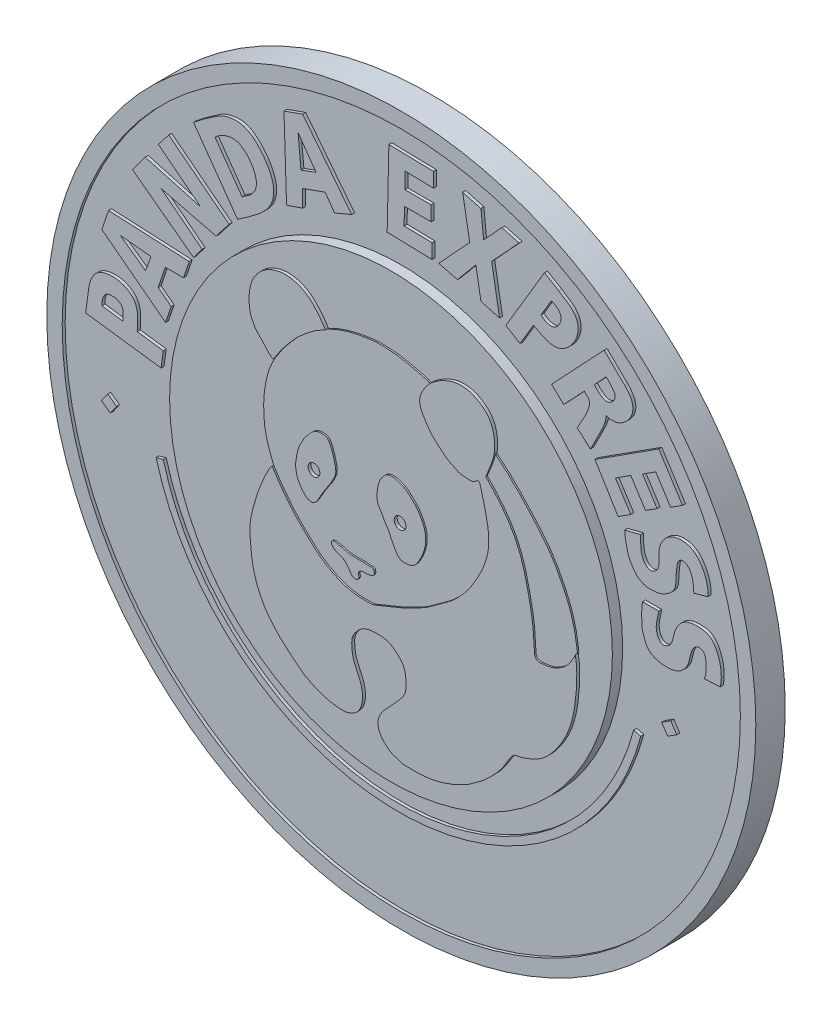
SolidWorks part; units mm, degrees
ref_plane "Front Plane" through (0, 0, 0) normal (0, 0, 1) x (1, 0, 0)
ref_plane "Top Plane" through (0, 0, 0) normal (0, 1, 0) x (1, 0, 0)
ref_plane "Right Plane" through (0, 0, 0) normal (1, 0, 0) x (0, 0, -1)
sketch "Sketch1" plane through (0, 0, 0) normal (0, 0, 1) x (1, 0, 0)
  line L0 (339.332, 1068.0205) -> (1796.7089, 1068.0205) construction
  line L1 (-19.4812, -2.2291) -> (-19.0488, -1.6286)
  line L2 (-19.4812, -2.2291) -> (-18.8807, -2.6615)
  line L3 (-19.0488, -1.6286) -> (-18.4483, -2.061)
  line L4 (-18.8807, -2.6615) -> (-18.4483, -2.061)
  line L5 (-19.265, -1.9289) -> (-18.6645, -2.3612) construction
  line L6 (-19.1809, -2.4453) -> (-18.7486, -1.8448) construction
  line L7 (-16.328, 0.8095) -> (-21.4546, 1.493)
  line L8 (18.5982, -2.1307) -> (19.2216, -1.7319)
  line L9 (18.5982, -2.1307) -> (19.007, -2.7476)
  line L10 (19.2216, -1.7319) -> (19.6303, -2.3488)
  line L11 (19.007, -2.7476) -> (19.6303, -2.3488)
  line L12 (-16.328, 0.8095) -> (-16.1813, 1.9098)
  line L13 (-21.4546, 1.493) -> (-21.3079, 2.5933)
  line L14 (-16.1813, 1.9098) -> (-17.9511, 2.1457)
  line L15 (-20.356, 2.4664) -> (-18.9346, 2.2769) construction
  line L16 (-18.9346, 2.2769) -> (-20.356, 2.4664)
  line L17 (-16.0257, 3.645) -> (-20.356, 6.9532)
  line L18 (-20.356, 6.9532) -> (-19.8974, 8.3016)
  line L19 (-19.8974, 8.3016) -> (-14.4158, 8.0372)
  line L20 (-14.4158, 8.0372) -> (-14.8071, 6.8869)
  line L21 (-14.8071, 6.8869) -> (-16.0419, 6.8869)
  line L22 (-16.0419, 6.8869) -> (-16.5291, 5.4546)
  line L23 (-16.5291, 5.4546) -> (-15.641, 4.7761)
  line L24 (-15.641, 4.7761) -> (-16.0257, 3.645)
  line L25 (-17.3832, 6.0121) -> (-19.0928, 7.2323)
  line L26 (-19.0928, 7.2323) -> (-17.016, 7.029)
  line L27 (-17.016, 7.029) -> (-17.3832, 6.0121)
  line L28 (-14.1219, 8.4186) -> (-18.2734, 11.5238)
  line L29 (-18.2734, 11.5238) -> (-17.4049, 12.685)
  line L30 (-17.4049, 12.685) -> (-13.6436, 11.6434)
  line L31 (-13.6436, 11.6434) -> (-16.5148, 13.8822)
  line L32 (-16.5148, 13.8822) -> (-15.8076, 14.7891)
  line L33 (-15.8076, 14.7891) -> (-11.7035, 11.5889)
  line L34 (-11.7035, 11.5889) -> (-12.5951, 10.4454)
  line L35 (-12.5951, 10.4454) -> (-16.3291, 11.3794)
  line L36 (-16.3291, 11.3794) -> (-13.5362, 9.2016)
  line L37 (-13.5362, 9.2016) -> (-14.1219, 8.4186)
  line L38 (-14.1219, 16.3735) -> (-11.1297, 12.1624)
  line L39 (-12.6612, 16.238) -> (-10.818, 13.644)
  line L40 (-7.7996, 14.6612) -> (-7.9742, 20.1206)
  line L41 (-7.9742, 20.1206) -> (-6.7044, 20.5722)
  line L42 (-6.7044, 20.5722) -> (-3.3753, 16.3234)
  line L43 (-4.5395, 15.8336) -> (-3.3753, 16.3234)
  line L44 (-4.5395, 15.8336) -> (-5.172, 16.7407)
  line L45 (-5.172, 16.7407) -> (-6.7044, 16.1956)
  line L46 (-6.7044, 16.1956) -> (-6.7044, 15.0331)
  line L47 (-6.7044, 15.0331) -> (-7.7996, 14.6612)
  line L48 (-6.8197, 17.2168) -> (-7.0148, 19.3221)
  line L49 (-7.0148, 19.3221) -> (-5.7899, 17.5994)
  line L50 (-5.7899, 17.5994) -> (-6.8197, 17.2168)
  line L51 (-0.8441, 21.7149) -> (-0.9604, 16.4903)
  line L52 (-0.8441, 21.7149) -> (0.2954, 21.6896)
  line L53 (-0.9604, 16.4903) -> (0.1792, 16.4649)
  line L54 (0.2635, 20.7001) -> (0.2389, 19.599)
  line L55 (0.2954, 21.6896) -> (2.1953, 21.6473)
  line L56 (2.1953, 21.6473) -> (2.1953, 20.6571)
  line L57 (2.1953, 20.6571) -> (0.2635, 20.7001)
  line L58 (0.2389, 19.599) -> (2.0359, 19.599)
  line L59 (2.0359, 19.599) -> (2.0359, 18.6011)
  line L60 (2.0359, 18.6011) -> (0.2167, 18.6011)
  line L61 (0.1909, 17.4402) -> (2.0962, 17.3978)
  line L62 (2.0962, 17.3978) -> (2.0962, 16.4105)
  line L63 (2.0962, 16.4105) -> (0.1792, 16.4649)
  line L64 (0.2167, 18.6011) -> (0.1909, 17.4402)
  line L65 (2.5434, 16.4105) -> (4.6494, 18.6907)
  line L66 (4.6494, 18.6907) -> (4.1742, 21.4149)
  line L67 (4.1742, 21.4149) -> (5.415, 21.0757)
  line L68 (5.415, 21.0757) -> (5.5944, 19.3138)
  line L69 (5.5944, 19.3138) -> (6.838, 20.6601)
  line L70 (6.838, 20.6601) -> (8.007, 20.3405)
  line L71 (8.007, 20.3405) -> (6.1448, 18.3245)
  line L72 (6.1448, 18.3245) -> (6.6794, 15.2603)
  line L73 (6.6794, 15.2603) -> (5.415, 15.6059)
  line L74 (5.415, 15.6059) -> (5.0699, 17.5842)
  line L75 (5.0699, 17.5842) -> (3.8207, 16.0897)
  line L76 (3.8207, 16.0897) -> (2.5434, 16.4105)
  line L77 (7.1051, 15.0331) -> (9.7332, 19.4533)
  line L78 (7.1051, 15.0331) -> (8.0751, 14.4563)
  line L79 (9.7332, 19.4533) -> (10.7033, 18.8765)
  line L80 (8.0751, 14.4563) -> (8.9844, 15.9855)
  line L81 (9.4951, 16.8446) -> (10.2149, 18.0551)
  line L82 (10.2149, 13.128) -> (13.7859, 16.9193)
  line L83 (13.7859, 16.9193) -> (15.1877, 15.5557)
  line L84 (12.8569, 10.6327) -> (11.9562, 11.4358)
  line L85 (10.2149, 13.128) -> (11.0408, 12.3501)
  line L86 (11.0408, 12.3501) -> (12.4388, 13.8344)
  line L87 (13.1299, 14.5705) -> (13.9228, 15.421)
  line L88 (13.163, 10.177) -> (17.5041, 12.9619)
  line L89 (17.5041, 12.9619) -> (19.1158, 10.4495)
  line L90 (19.1158, 10.4495) -> (18.31, 9.9325)
  line L91 (18.31, 9.9325) -> (17.2969, 11.5117)
  line L92 (17.2969, 11.5117) -> (16.4026, 10.938)
  line L93 (16.4026, 10.938) -> (17.3902, 9.3984)
  line L94 (17.3902, 9.3984) -> (16.6002, 8.8916)
  line L95 (16.6002, 8.8916) -> (15.6008, 10.4495)
  line L96 (15.6008, 10.4495) -> (14.5586, 9.7809)
  line L97 (14.5586, 9.7809) -> (15.6008, 8.1562)
  line L98 (15.6008, 8.1562) -> (14.7409, 7.6046)
  line L99 (14.7409, 7.6046) -> (13.163, 10.177)
  line L100 (19.8907, 5.6627) -> (20.842, 5.9313)
  line L101 (15.1877, 7.029) -> (16.2747, 7.3088)
  line L102 (21.6804, 1.0421) -> (20.6063, 0.9853)
  line L103 (16.4026, 3.4174) -> (17.5041, 3.4174)
  line L104 (-16.4657, -4.4254) -> (-15.9828, -4.2956)
  line L105 (15.9993, -4.2338) -> (16.4827, -4.3617)
  line L106 (-19.7778, -8.1941) -> (-18.3448, -7.6877)
  line L107 (-18.3448, -7.6877) -> (-18.7074, -6.6618)
  line L108 (-18.7074, -6.6618) -> (-19.1206, -6.8078)
  line L109 (-19.1206, -6.8078) -> (-18.9255, -7.36)
  line L110 (-18.9255, -7.36) -> (-19.3406, -7.5067)
  line L111 (-17.2786, -7.2591) -> (-17.7047, -7.4011)
  circle A0 centre (0, 0) radius 24.1
  circle A2 centre (0.8192, 0.7097) radius 0.4
  circle A3 centre (-5.0357, 0.9092) radius 0.4
  circle A4 centre (0, 0) radius 23.05
  arc A8 (-16.4657, -4.4254) -> (16.4827, -4.3617) centre (0, 0) ccw
  arc A9 (12.0045, 11.3927) -> (11.9591, 11.4404) centre (0, 0) ccw
  arc A10 (-15.9828, -4.2956) -> (15.9993, -4.2338) centre (0, 0) ccw
  circle A11 centre (0, 0) radius 15.05
  spline S0 degree 3 poles (-21.3079, 2.5933) (-21.2691, 3.0317) (-21.1768, 3.6983) (-20.5495, 4.4203) (-19.7315, 4.6028) (-18.8263, 4.4892) (-17.7876, 3.7164) (-17.9169, 2.6645) (-17.9511, 2.1457) knots 0 0 0 0 0.212608 0.302228 0.435295 0.58816 0.72772 1 1 1 1
  spline S1 degree 3 poles (-20.356, 2.4664) (-20.3596, 2.708) (-20.3083, 3.0361) (-20.0437, 3.3225) (-19.8441, 3.3874) (-19.6429, 3.3957) (-19.4314, 3.3931) (-19.2421, 3.3315) (-19.0854, 3.2283) (-18.9615, 3.0995) (-18.903, 2.9079) (-18.9209, 2.6293) (-18.9309, 2.419) (-18.9346, 2.2769) knots 0 0 0 0 0.24967 0.31684 0.388224 0.45752 0.523447 0.60401 0.657003 0.715094 0.783365 0.85461 1 1 1 1
  spline S2 degree 3 poles (-14.1219, 16.3735) (-13.7209, 16.7208) (-13.0883, 17.1571) (-12.271, 17.7302) (-11.5963, 17.9267) (-10.9205, 17.9501) (-10.2597, 17.6972) (-9.7098, 17.2041) (-9.2288, 16.6239) (-8.862, 15.963) (-8.6469, 15.3064) (-8.6778, 14.6592) (-8.8637, 14.1319) (-9.1362, 13.7413) (-9.417, 13.4477) (-9.7019, 13.1931) (-10.037, 12.9534) (-10.3472, 12.697) (-10.7324, 12.4509) (-10.9743, 12.2645) (-11.1297, 12.1624) knots 0 0 0 0 0.137806 0.202861 0.258965 0.319388 0.376747 0.439138 0.510699 0.573298 0.636319 0.688639 0.739908 0.780606 0.812336 0.846158 0.880461 0.92011 0.951368 1 1 1 1
  spline S3 degree 3 poles (-12.6612, 16.238) (-12.4563, 16.4417) (-12.1084, 16.6477) (-11.5932, 16.7783) (-11.2363, 16.7638) (-10.8923, 16.6366) (-10.6281, 16.4146) (-10.3806, 16.2025) (-10.2419, 15.9574) (-10.08, 15.7506) (-9.9673, 15.4995) (-9.8712, 15.2122) (-9.8326, 14.8948) (-9.8834, 14.5632) (-10.0424, 14.2696) (-10.3388, 13.9337) (-10.6484, 13.7894) (-10.818, 13.644) knots 0 0 0 0 0.150292 0.209994 0.278717 0.335693 0.400225 0.460062 0.506204 0.547788 0.598508 0.650561 0.70761 0.76587 0.824644 0.881692 1 1 1 1
  spline S4 degree 3 poles (-7.8698, -0.2966) (-8.0954, 0.2301) (-8.4492, 1.1743) (-8.5703, 2.5467) (-8.5515, 3.6093) (-8.3835, 4.488) (-8.1929, 5.2865) (-7.9297, 5.779) (-7.7996, 6.0464) knots 0 0 0 0 0.262924 0.455258 0.626555 0.746828 0.863807 1 1 1 1
  spline S5 degree 3 poles (-7.7996, 6.0464) (-7.6451, 6.2665) (-7.4204, 6.6545) (-7.0465, 7.1537) (-6.6804, 7.5866) (-6.3099, 8.0223) (-5.8659, 8.4497) (-5.3867, 8.825) (-4.8971, 9.2131) (-4.387, 9.4734) (-3.8724, 9.7419) (-3.2734, 9.9751) (-2.5437, 10.1984) (-1.7558, 10.3499) (-0.7272, 10.5033) (0.028, 10.4188) (0.517, 10.391) knots 0 0 0 0 0.080975 0.134778 0.187605 0.25173 0.306954 0.372796 0.435137 0.494459 0.544747 0.60996 0.687673 0.774238 0.851502 1 1 1 1
  spline S6 degree 3 poles (0.517, 10.391) (0.7571, 10.363) (1.1301, 10.2878) (1.6851, 10.1723) (2.1805, 10.0244) (2.5544, 9.9487) (2.7165, 9.8349) knots 0 0 0 0 0.318288 0.501169 0.746278 1 1 1 1
  spline S7 degree 3 poles (2.7165, 9.8349) (2.7585, 9.8259) (2.7327, 9.8017) (2.6898, 9.7669) (2.6476, 9.7124) (2.603, 9.6398) (2.5377, 9.5744) (2.4953, 9.4826) (2.4254, 9.3973) (2.3776, 9.2895) (2.3059, 9.1789) (2.2534, 9.0434) (2.1887, 8.8944) (2.1538, 8.732) (2.1435, 8.5478) (2.1783, 8.3137) (2.2639, 8.0294) (2.4362, 7.7403) (2.6287, 7.4486) (2.8286, 7.1514) (3.0779, 6.8852) (3.3548, 6.607) (3.69, 6.3213) (4.0714, 6.0472) (4.481, 5.8298) (4.913, 5.6227) (5.3993, 5.6193) (5.838, 5.5698) (6.0966, 5.905) (6.2435, 5.7688) (6.27, 5.658) (6.3218, 5.5071) (6.3605, 5.3336) (6.4745, 4.9931) (6.5291, 4.6383) (6.6488, 4.174) (6.8141, 3.4444) (6.8792, 2.7588) (6.819, 2.2769) knots 0 0 0 0 0.004783 0.008508 0.016209 0.023904 0.032742 0.042051 0.052291 0.063813 0.075279 0.089559 0.104863 0.1213 0.136341 0.156965 0.188092 0.219871 0.251904 0.287379 0.321184 0.355103 0.398707 0.445985 0.487792 0.530607 0.579554 0.623786 0.654803 0.659487 0.677019 0.686171 0.704891 0.727287 0.787897 0.806239 0.863282 1 1 1 1
  spline S8 degree 3 poles (6.819, 2.2769) (6.819, 2.0161) (6.7092, 1.6228) (6.5071, 0.999) (6.2546, 0.4026) (5.9145, -0.1762) (5.4655, -0.9295) (4.8863, -1.5979) (4.1145, -2.3101) (3.3615, -2.7838) (2.6307, -3.396) (1.8173, -3.786) (1.0012, -4.215) (0.2125, -4.521) (-0.4801, -4.7998) (-0.967, -5.0314) (-1.4954, -5.0428) (-2.1511, -5.0376) (-2.9852, -4.8681) (-3.7859, -4.5156) (-4.6591, -3.9915) (-5.5404, -3.1815) (-6.7534, -1.9752) (-7.4558, -0.951) (-7.8698, -0.2966) knots 0 0 0 0 0.038566 0.060844 0.098257 0.135206 0.161303 0.229508 0.266609 0.318218 0.362343 0.408696 0.452572 0.500532 0.534926 0.565086 0.579479 0.613416 0.663457 0.705415 0.743958 0.815443 0.883791 1 1 1 1
  spline S9 degree 3 poles (-7.7996, 6.0464) (-8.1142, 6.1934) (-8.4061, 6.6917) (-8.9684, 7.1134) (-9.1868, 7.5516) (-9.3506, 7.8873) (-9.4347, 8.3363) (-9.4676, 8.9461) (-9.3813, 9.6739) (-9.0254, 10.4197) (-8.4574, 11.0181) (-7.6635, 11.3928) (-6.6098, 11.5101) (-5.4899, 11.0879) (-4.7556, 10.2648) (-4.3819, 9.7678) (-4.2674, 9.5361) knots 0 0 0 0 0.091045 0.156662 0.189319 0.225208 0.259759 0.314673 0.394281 0.459416 0.540292 0.617479 0.697593 0.828696 0.928545 1 1 1 1
  spline S10 degree 3 poles (2.742, 9.8124) (2.8815, 9.9916) (3.2342, 10.2729) (3.8223, 10.6189) (4.495, 10.8717) (5.3292, 10.9228) (6.1699, 10.5971) (6.965, 9.9438) (7.2573, 8.9642) (7.269, 7.9936) (6.9947, 7.1881) (6.785, 6.6958) (6.6353, 6.3436) (6.7624, 6.2308) (6.895, 6.0725) (7.017, 5.9709) (7.1051, 5.8757) knots 0 0 0 0 0.074542 0.147752 0.224877 0.309979 0.41722 0.515404 0.639072 0.738685 0.83491 0.910197 0.931048 0.943333 0.961579 1 1 1 1
  spline S11 degree 3 poles (-7.8698, -0.2966) (-7.9669, -0.372) (-8.1093, -0.5873) (-8.3686, -1.1056) (-8.609, -1.6814) (-8.8668, -2.3248) (-9.0417, -2.9481) (-9.264, -3.6956) (-9.4298, -4.5934) (-9.3613, -5.4091) (-9.3053, -6.1456) (-9.1931, -6.8564) (-8.9337, -7.8216) (-8.3664, -8.9775) (-7.4864, -10.0166) (-6.5688, -10.7863) (-5.8603, -11.3886) (-5.1793, -11.7627) (-4.367, -12.1085) (-3.5858, -12.2564) (-2.8615, -12.2789) (-2.4465, -12.1255) (-1.8999, -11.7656) (-1.687, -10.9971) (-1.7828, -10.2013) (-2.0566, -9.5521) (-2.3907, -8.9202) (-2.4659, -8.2782) (-2.4794, -7.7623) (-2.3011, -7.3166) (-2.039, -7.0486) (-1.7478, -6.7699) (-1.495, -6.6845) (-1.1715, -6.5969) (-0.8714, -6.5881) (-0.5143, -6.5754) (-0.1409, -6.6304) (0.2891, -6.7936) (0.7059, -7.1433) (1.131, -7.6086) (1.225, -8.2488) (1.2466, -8.8123) (1.1152, -9.3303) (0.8325, -9.6422) (0.441, -10.1058) (-0.006, -10.5386) (-0.4673, -11.0901) (-0.7105, -11.5884) (-0.6845, -12.0178) (-0.5581, -12.3443) (-0.4095, -12.6017) (-0.1202, -12.8828) (0.2279, -13.1621) (0.6218, -13.2389) (0.9291, -13.3723) (1.2092, -13.4066) (1.5533, -13.3952) (1.9399, -13.403) (2.3733, -13.3907) (2.8331, -13.3379) (3.2975, -13.246) (3.7367, -13.1264) (4.1564, -12.9826) (4.542, -12.8403) (4.9967, -12.5882) (5.4073, -12.4174) (5.6956, -12.1817) (5.9279, -12.0253) (6.3206, -11.7521) (7.048, -11.0999) (7.8304, -10.2552) (8.2495, -9.4122) (8.5575, -9.0662) (8.7914, -9.0098) (9.1141, -8.9679) (9.478, -8.8285) (9.9237, -8.6465) (10.352, -8.4183) (10.894, -7.9721) (11.468, -7.2875) (11.9927, -6.4407) (12.5497, -5.1606) (12.8285, -3.3719) (12.8686, -1.8572) (12.7298, -1.0883) knots 0 0 0 0 0.007011 0.014783 0.033549 0.043071 0.054853 0.070952 0.088248 0.107232 0.118017 0.131016 0.148787 0.175674 0.20476 0.226792 0.244992 0.258357 0.271565 0.29594 0.303926 0.313058 0.321071 0.341004 0.354332 0.367388 0.381474 0.395309 0.404361 0.410961 0.422437 0.425735 0.43417 0.437336 0.44516 0.45138 0.458007 0.466877 0.477543 0.48934 0.502235 0.513644 0.522123 0.532268 0.537492 0.557326 0.568112 0.579108 0.58845 0.591926 0.59936 0.605375 0.61525 0.624546 0.628148 0.63458 0.64061 0.648096 0.656937 0.665671 0.674836 0.684305 0.691972 0.700514 0.708012 0.722054 0.725913 0.729489 0.738257 0.753548 0.786033 0.803683 0.808277 0.811877 0.817215 0.827205 0.834171 0.845129 0.855095 0.874603 0.896509 0.912539 0.955058 1 1 1 1
  spline S12 degree 3 poles (12.7298, -1.0883) (12.6797, -1.2231) (12.56, -1.4426) (12.2508, -1.9657) (11.7266, -2.393) (11.0363, -2.6958) (10.5826, -2.7318) (10.2423, -2.7706) (10.0738, -2.6715) (9.9407, -2.5319) (9.966, -2.3796) (9.9456, -2.2453) (9.9426, -2.0798) (9.9261, -1.8665) (9.8968, -1.4785) (9.8741, -1.0693) (9.7722, -0.1933) (9.5358, 0.9691) (9.1873, 2.4844) (8.6476, 3.8078) (7.9718, 4.8579) (7.4802, 5.4523) (7.2443, 5.7152) knots 0 0 0 0 0.034675 0.060301 0.146525 0.192052 0.240064 0.257138 0.271971 0.286029 0.300164 0.306563 0.318999 0.339993 0.358311 0.413001 0.438973 0.571315 0.699318 0.81421 0.914445 1 1 1 1
  spline S13 degree 3 poles (7.1051, 5.8757) (7.1279, 5.8511) (7.1758, 5.7989) (7.2194, 5.743) (7.2443, 5.7152) knots 0 0 0 0 0.474339 1 1 1 1
  spline S14 degree 3 poles (7.2065, 7.9328) (7.2419, 7.8726) (7.3373, 7.765) (7.537, 7.6278) (7.7636, 7.3937) (8.0698, 7.1947) (8.28, 6.9221) (8.4856, 6.7412) (8.69, 6.5563) (8.8995, 6.3265) (9.1296, 6.0794) (9.4861, 5.7124) (9.8089, 5.3025) (10.1801, 4.9279) (10.4244, 4.6174) (10.7123, 4.2695) (10.9886, 3.8516) (11.2824, 3.4158) (11.5191, 2.9264) (11.801, 2.4395) (12.0053, 1.9288) (12.222, 1.4589) (12.3778, 0.9725) (12.5313, 0.4458) (12.651, -0.1163) (12.7048, -0.6277) (12.7981, -0.9652) (12.7298, -1.0883) knots 0 0 0 0 0.019122 0.039215 0.066393 0.108561 0.138517 0.160369 0.183882 0.214401 0.245895 0.276915 0.355239 0.389296 0.421963 0.463986 0.513572 0.559828 0.608533 0.663052 0.71455 0.759793 0.805469 0.854908 0.911185 0.962305 1 1 1 1
  spline S15 degree 3 poles (-5.8531, 2.1457) (-5.8137, 2.1982) (-5.7778, 2.3755) (-5.5778, 2.5904) (-5.3744, 2.8763) (-5.0924, 3.1386) (-4.748, 3.3433) (-4.4246, 3.3105) (-4.1622, 3.3021) (-4.0161, 3.1106) (-3.8488, 2.7995) (-3.7001, 2.3487) (-3.5662, 1.8312) (-3.5309, 1.4066) (-3.7025, 1.0683) (-3.8202, 0.7985) (-4.0638, 0.4685) (-4.3018, 0.0853) (-4.6463, -0.4561) (-4.8253, -0.8829) (-5.0593, -1.0351) knots 0 0 0 0 0.027214 0.073863 0.120798 0.175728 0.237147 0.280267 0.312444 0.341416 0.37515 0.464016 0.53885 0.60401 0.635554 0.697289 0.728278 0.808417 0.88794 1 1 1 1
  spline S16 degree 3 poles (-5.0593, -1.0351) (-5.1488, -1.084) (-5.296, -1.0515) (-5.4843, -1.0019) (-5.6583, -0.868) (-5.837, -0.669) (-6.0659, -0.3455) (-6.221, 0.0555) (-6.3054, 0.5295) (-6.244, 1.0146) (-6.1494, 1.4999) (-6.0165, 1.8943) (-5.8955, 2.0894) (-5.8531, 2.1457) knots 0 0 0 0 0.072528 0.112402 0.148382 0.238596 0.317746 0.451456 0.565272 0.683898 0.823832 0.946187 1 1 1 1
  spline S17 degree 3 poles (-3.8049, -2.9373) (-3.856, -2.8116) (-3.8647, -2.6966) (-3.755, -2.6053) (-3.5802, -2.5829) (-3.3791, -2.6817) (-3.1383, -2.6805) (-2.8611, -2.7796) (-2.5219, -2.8411) (-2.0754, -2.8499) (-1.5965, -2.8326) (-1.2558, -2.8728) (-0.9613, -2.8792) (-0.9425, -2.9959) (-0.9276, -3.1123) (-0.9574, -3.2911) (-1.1954, -3.37) (-1.442, -3.4336) (-1.7167, -3.3825) (-1.9185, -3.4731) (-2.0427, -3.6436) (-1.9591, -3.8304) (-2.0161, -4.0345) (-2.1944, -4.1119) (-2.4309, -4.0847) (-2.5621, -3.8441) (-2.7332, -3.6292) (-2.9128, -3.411) (-3.1621, -3.2276) (-3.4418, -3.1858) (-3.6759, -3.0608) (-3.8049, -2.9373) (-3.856, -2.8116) (-3.8647, -2.6966) knots -0.069641 -0.0386 -0.005489 0 0.017312 0.037391 0.051206 0.088306 0.125243 0.148544 0.208577 0.265756 0.332972 0.400272 0.42114 0.43379 0.44282 0.471286 0.497085 0.537674 0.577476 0.607463 0.623843 0.658289 0.682487 0.701901 0.73331 0.770198 0.806365 0.848099 0.885786 0.930359 0.9614 0.994511 1 1.017312 1.037391 1.051206 only from (-3.8442, -2.8376) to (-3.8442, -2.8376)
  spline S18 degree 3 poles (-0.7138, 1.0524) (-0.7458, 1.3812) (-0.7605, 1.6915) (-0.7005, 2.0488) (-0.6214, 2.448) (-0.3838, 2.8453) (-0.0835, 3.147) (0.3836, 3.2107) (0.8128, 3.0761) (1.2487, 2.8736) (1.5796, 2.5436) (1.9609, 2.1911) (2.2655, 1.702) (2.5565, 1.0762) (2.5938, 0.3573) (2.3868, -0.3333) (2.1319, -0.856) (1.8112, -1.3429) (1.32, -1.5002) (0.7796, -1.4799) (0.4925, -1.0312) (0.2404, -0.6025) (0.0577, -0.1057) (-0.2756, 0.3043) (-0.438, 0.7306) (-0.7138, 1.0524) (-0.7458, 1.3812) (-0.7605, 1.6915) knots -0.10057 -0.055269 -0.031008 0 0.021936 0.04495 0.087916 0.119709 0.157131 0.186449 0.229202 0.26531 0.302252 0.341943 0.391484 0.441273 0.508862 0.560753 0.615141 0.651568 0.697769 0.734975 0.772439 0.817527 0.85896 0.89943 0.944731 0.968992 1 1.021936 1.04495 1.087916 only from (-0.7455, 1.4167) to (-0.7455, 1.4167)
  spline S19 degree 3 poles (10.7033, 18.8765) (10.9761, 18.6947) (11.4462, 18.4434) (11.959, 17.8662) (12.0828, 17.1068) (11.7876, 16.3466) (11.2829, 15.7715) (10.6982, 15.4417) (10.1171, 15.4592) (9.5478, 15.6787) (9.2006, 15.8769) (8.9844, 15.9855) knots 0 0 0 0 0.155202 0.252119 0.353417 0.502545 0.622306 0.711778 0.810984 0.885243 1 1 1 1
  spline S20 degree 3 poles (10.2149, 18.0551) (10.3341, 17.9857) (10.5592, 17.8891) (10.8213, 17.6117) (10.8956, 17.2447) (10.7485, 16.9257) (10.5773, 16.674) (10.3286, 16.5374) (10.0665, 16.5486) (9.7723, 16.6225) (9.6005, 16.7692) (9.4951, 16.8446) knots 0 0 0 0 0.142608 0.248615 0.3816 0.498063 0.60104 0.691827 0.774831 0.865222 1 1 1 1
  spline S21 degree 3 poles (15.1877, 15.5557) (15.4066, 15.3456) (15.7668, 14.8999) (15.7524, 14.0499) (15.3309, 13.4624) (14.7011, 13.0373) (14.1804, 13.0364) (13.9228, 13.1363) knots 0 0 0 0 0.242155 0.419875 0.622755 0.78372 1 1 1 1
  spline S22 degree 3 poles (13.9228, 13.1363) (13.9129, 13.0434) (13.8977, 12.8314) (13.7446, 12.3826) (13.3709, 11.6539) (13.0709, 11.0198) (12.8569, 10.6327) knots 0 0 0 0 0.102575 0.23152 0.51558 1 1 1 1
  spline S23 degree 3 poles (11.9562, 11.4358) (12.1055, 11.679) (12.3069, 12.0727) (12.5882, 12.572) (12.7254, 12.939) (12.8229, 13.2515) (12.7403, 13.6003) (12.522, 13.7234) (12.4388, 13.8344) knots 0 0 0 0 0.314516 0.488901 0.630486 0.747958 0.84444 1 1 1 1
  spline S24 degree 3 poles (13.1299, 14.5705) (13.2303, 14.4112) (13.4534, 14.2205) (13.7953, 13.9719) (14.1315, 13.9914) (14.3544, 14.1697) (14.511, 14.3757) (14.5802, 14.6679) (14.3078, 15.0234) (14.1161, 15.266) (13.9228, 15.421) knots 0 0 0 0 0.184548 0.297295 0.411883 0.489672 0.576662 0.67143 0.761868 1 1 1 1
  spline S25 degree 3 poles (16.2747, 7.3088) (16.2779, 6.9471) (16.2395, 6.4066) (16.4878, 5.815) (16.7993, 5.5009) (17.2293, 5.57) (17.5641, 6.0011) (17.4637, 6.672) (17.5751, 7.4217) (18.0317, 8.0838) (18.8517, 8.4593) (19.8796, 8.2702) (20.6495, 7.2973) (20.8876, 6.4558) (20.842, 5.9313) knots 0 0 0 0 0.118465 0.166211 0.204261 0.250626 0.284914 0.370065 0.453977 0.525647 0.618546 0.728729 0.832231 1 1 1 1
  spline S26 degree 3 poles (19.8907, 5.6627) (19.8538, 5.8307) (19.8728, 6.1831) (19.743, 6.6735) (19.5277, 7.0697) (19.1986, 7.2175) (18.8935, 7.1557) (18.7474, 6.845) (18.7185, 6.5025) (18.6749, 6.1104) (18.6688, 5.7454) (18.6421, 5.4279) (18.5057, 5.0731) (18.1929, 4.8008) (17.7871, 4.5573) (17.3748, 4.4273) (16.9975, 4.4357) (16.6504, 4.4181) (16.3145, 4.5464) (15.9275, 4.7924) (15.7623, 5.0872) (15.6622, 5.235) knots 0 0 0 0 0.068424 0.138794 0.202186 0.239054 0.276469 0.312498 0.365649 0.415257 0.469432 0.511705 0.541628 0.618954 0.670054 0.731473 0.787786 0.820419 0.869002 0.92833 1 1 1 1
  spline S27 degree 3 poles (15.6622, 5.235) (15.4917, 5.4644) (15.3222, 6.0732) (15.1965, 6.6823) (15.1877, 7.029) knots 0 0 0 0 0.449772 1 1 1 1
  spline S28 degree 3 poles (17.5041, 3.4174) (17.4153, 2.9415) (17.138, 2.2442) (17.7407, 1.4627) (18.3555, 1.7856) (18.491, 2.3706) (18.6517, 3.0625) (19.2186, 3.7652) (20.0968, 3.8792) (21.1471, 3.7445) (21.765, 2.4853) (21.7885, 1.5348) (21.6804, 1.0421) knots 0 0 0 0 0.166113 0.213941 0.272936 0.34154 0.40606 0.505933 0.610916 0.681573 0.837609 1 1 1 1
  spline S29 degree 3 poles (20.6063, 0.9853) (20.7317, 1.3259) (20.7426, 1.8125) (20.6613, 2.5536) (20.1333, 2.706) (19.7614, 2.333) (19.6265, 1.8181) (19.5052, 1.1569) (18.9086, 0.4499) (17.8399, 0.3253) (16.7921, 0.6194) (16.508, 1.341) (16.3538, 1.8354) (16.3417, 2.5146) (16.3241, 3.0398) (16.4026, 3.4174) knots 0 0 0 0 0.111139 0.169018 0.211891 0.254869 0.321101 0.382254 0.469556 0.595042 0.710524 0.783644 0.830558 0.8775 1 1 1 1
  spline S30 degree 3 poles (-19.7778, -8.1941) (-20.0155, -7.8158) (-20.2878, -7.2097) (-20.3081, -6.3004) (-19.8923, -5.7241) (-19.2343, -5.4473) (-18.3715, -5.3243) (-17.4852, -6.0763) (-17.3647, -6.8558) (-17.2786, -7.2591) knots 0 0 0 0 0.210697 0.30674 0.413443 0.520528 0.638291 0.804261 1 1 1 1
  spline S31 degree 3 poles (-19.3406, -7.5067) (-19.4117, -7.5159) (-19.5917, -7.6118) (-19.7001, -7.4535) (-19.7579, -7.276) (-19.8218, -7.0186) (-19.8126, -6.7091) (-19.6652, -6.3974) (-19.3667, -6.12) (-18.94, -5.9897) (-18.5215, -5.9875) (-18.0925, -6.1905) (-17.8637, -6.6168) (-17.7657, -7.0497) (-17.7512, -7.2971) (-17.7047, -7.4011) knots 0 0 0 0 0.065997 0.085275 0.119822 0.193861 0.262473 0.324025 0.421836 0.527721 0.617953 0.698927 0.835003 0.924051 1 1 1 1
  spline S32 degree 3 poles (-18.6437, -9.7101) (-18.6215, -9.3737) (-18.3505, -9.0504) (-17.8828, -8.7282) (-17.1195, -8.5941) (-16.5927, -9.2074) (-16.7928, -9.9113) (-17.2735, -10.2413) (-17.7622, -10.4186) (-18.2138, -10.3806) (-18.5709, -10.0698) (-18.6437, -9.7101) (-18.6215, -9.3737) (-18.3505, -9.0504) knots -0.186247 -0.120465 -0.037532 0 0.055592 0.176983 0.306298 0.425196 0.537049 0.653164 0.724224 0.813753 0.879535 0.962468 1 1.055592 1.176983 1.306298 only from (-18.6065, -9.4143) to (-18.6065, -9.4143)
  spline S33 degree 3 poles (-19.1667, -9.2142) (-18.7772, -8.6272) (-18.2461, -8.283) (-17.7066, -8.1017) (-17.0337, -8.1347) (-16.447, -8.6328) (-16.1918, -9.3275) (-16.2456, -10.0222) (-16.6204, -10.4764) (-17.0581, -10.8252) (-17.5785, -10.9349) (-18.1233, -10.9761) (-18.692, -10.6219) (-19.0875, -10.024) (-19.1667, -9.2142) (-18.7772, -8.6272) (-18.2461, -8.283) knots -0.262157 -0.167002 -0.092784 0 0.053121 0.120463 0.190117 0.270707 0.364539 0.432375 0.495297 0.557849 0.618073 0.672691 0.737843 0.832998 0.907216 1 1.053121 1.120463 1.190117 only from (-18.6645, -8.5835) to (-18.6645, -8.5835)
  point P12 (-18.6645, -2.3612)
  dimension "D1" = 48.2
  dimension "D12" = 0.8
  dimension "D13" = 0.8
  dimension "D16" = 46.1
  dimension "D2" = 30.1
  dimension "D3" = 0.74
  dimension "D4" = 0.74
  dimension "D5" = 0.74
  dimension "D6" = 0.74
  dimension "D7" = 1.11
  dimension "D8" = 1.45
  dimension "D9" = 1.45
  dimension "D10" = 1.15
  dimension "D11" = 1.15
  dimension "D14" = 0.99
  dimension "D15" = 0.9979
extrude "Boss-Extrude2" add sketch "Sketch1" against normal blind 2 contours A0
extrude "Cut-Extrude1" cut sketch "Sketch1<5>" against normal blind 0.2 contours A4
sketch "Sketch1<5>" plane through (0, 0, 0) normal (0, 0, 1) x (1, 0, 0) same geometry as "Sketch1"
extrude "Boss-Extrude3" add sketch "Sketch1<6>" along normal blind 0.7 separate body contours A11
sketch "Sketch1<6>" plane through (0, 0, 0) normal (0, 0, 1) x (1, 0, 0) same geometry as "Sketch1"
extrude "Boss-Extrude4" add sketch "Sketch1<9>" along normal blind 0.2 from offset 0.7 contours S13 S10 S7 S8 S11 S12 | S9 S5 region at (2.565, -4.584, 0) region at (-7.2885, 9.1755, 0)
sketch "Sketch1<9>" plane through (0, 0, 0) normal (0, 0, 1) x (1, 0, 0) same geometry as "Sketch1"
extrude "Boss-Extrude5" add sketch "Sketch1<10>" along normal blind 0.1 from offset 0.7 contours S8 S7 S6 S5 S4 S17 S15 S16 S18 region at (-1.0892, 2.9599, 0)
sketch "Sketch1<10>" plane through (0, 0, 0) normal (0, 0, 1) x (1, 0, 0) same geometry as "Sketch1"
extrude "Boss-Extrude6" add sketch "Sketch1<13>" against normal through all contours S0 L13 L7 L12 L14 L16 S1 | L24 L23 L22 L21 L20 L19 L18 L17 L26 L27 L25 | L37 L36 L35 L34 L33 L32 L31 L30 L29 L28 | S2 L38 L39 S3 | L47 L46 L45 L44 L43 L42 L41 L40 L49 L50 L48 | L64 L60 L59 L58 L54 L57 L56 L55 L52 L51 L53 L63 L62 L61 | L76 L75 L74 L73 L72 L71 L70 L69 L68 L67 L66 L65 | S19 L79 L77 L78 L80 L81 S20 | S23 L84 S22 S21 L83 L82 L85 L86 S24 L87 | L99 L98 L97 L96 L95 L94 L93 L92 L91 L90 L89 L88 | S27 S26 L100 S25 L101 | S29 L102 S28 L103 region at (-18.8827, 1.2154, 0) region at (-18.145, 5.3591, 0) region at (-14.9891, 11.6161, 0) region at (-9.3649, 16.6381, 0) region at (-7.812, 17.3933, 0) region at (0.3953, 19.0823, 0) region at (5.3436, 18.3171, 0) region at (8.4794, 17.2074, 0) region at (13.2423, 13.9831, 0) region at (16.0152, 10.4848, 0) region at (18.0048, 6.3858, 0) region at (18.9875, 2.1276, 0)
sketch "Sketch1<13>" plane through (0, 0, 0) normal (0, 0, 1) x (1, 0, 0) same geometry as "Sketch1"
extrude "Boss-Extrude7" add sketch "Sketch1<14>" along normal blind 0.2 from offset 0.7 contours S16 S15 A3 | S18 A2 | S17 region at (-3.6818, 2.0614, 0) region at (-2.3755, -3.1935, 0) region at (2.4986, 0.4121, 0)
sketch "Sketch1<14>" plane through (0, 0, 0) normal (0, 0, 1) x (1, 0, 0) same geometry as "Sketch1"
extrude "Boss-Extrude8" add sketch "Sketch1<15>" along normal blind 0.2 from offset 0.7 separate body contours L2 L4 L3 L1 | L9 L11 L10 L8 region at (-18.9648, -2.145, 0) region at (19.1143, -2.2397, 0)
sketch "Sketch1<15>" plane through (0, 0, 0) normal (0, 0, 1) x (1, 0, 0) same geometry as "Sketch1"
extrude "Boss-Extrude9" add sketch "Sketch1<16>" along normal blind 0.2 separate body contours A10 L104 A8 L105 region at (-16.1325, -4.7019, 0)
sketch "Sketch1<16>" plane through (0, 0, 0) normal (0, 0, 1) x (1, 0, 0) same geometry as "Sketch1"
extrude "Boss-Extrude11" add sketch "Sketch1<18>" along normal blind 0.1 from offset 0.7 contours S14 S10 S13 S12 region at (10.1457, 2.1205, 0)
sketch "Sketch1<18>" plane through (0, 0, 0) normal (0, 0, 1) x (1, 0, 0) same geometry as "Sketch1"
